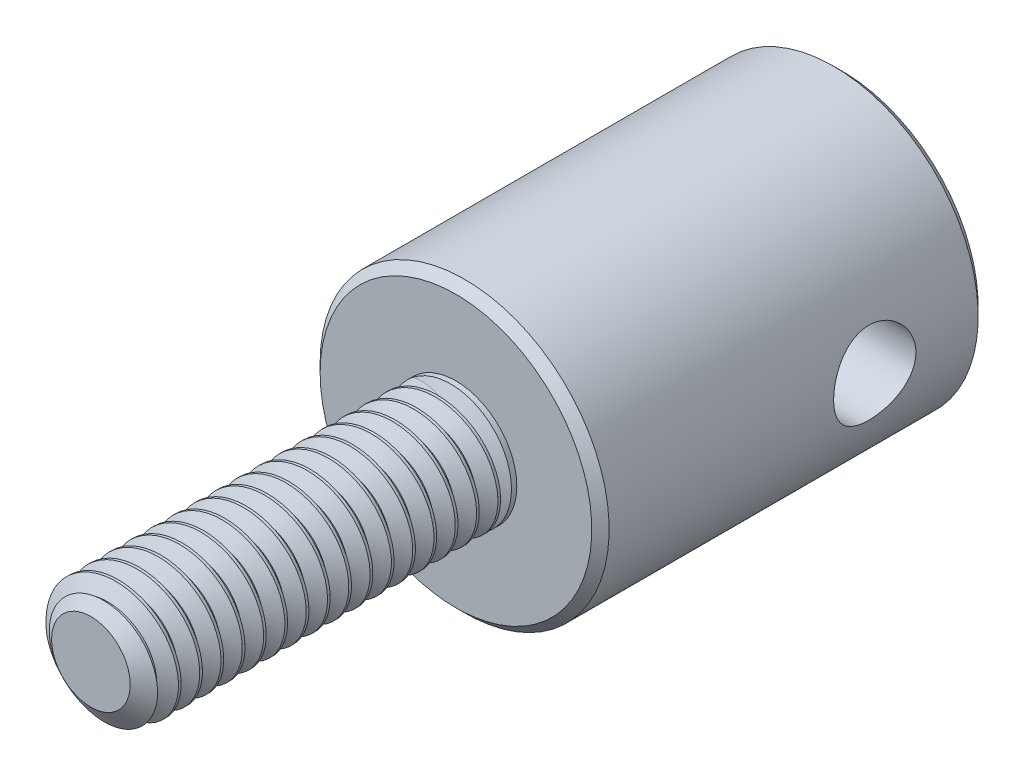
SolidWorks part; units mm, degrees
ref_plane "Front Plane" through (0, 0, 0) normal (0, 0, 1) x (1, 0, 0)
ref_plane "Top Plane" through (0, 0, 0) normal (0, 1, 0) x (1, 0, 0)
ref_plane "Right Plane" through (0, 0, 0) normal (1, 0, 0) x (0, 0, -1)
sketch "Sketch1" plane through (0, 0, 0) normal (0, 0, 1) x (1, 0, 0)
  circle A0 centre (0, 0) radius 2
  dimension "OD" = 4
extrude "Extrude1" add sketch "Sketch1" against normal blind 12
sketch "Sketch2" plane through (0, 0, 0) normal (0, 0, 1) x (1, 0, 0)
  circle A0 centre (0, 0) radius 2 construction
  circle A1 centre (0, 0) radius 2
curve "Helix/Spiral1" pitch 0.7 height 12.7 radius 2 centre (0, 0, 0) axis (0, 0, -1) start towards (0, 1, 0) parameters "pitch"=0.7
sketch "Sketch3" plane through (0, 0, 0) normal (1, 0, 0) x (0, 0, -1)
  line L0 (-0.6125, 2) -> (-0.35, 1.5453)
  line L1 (-0.35, 1.5453) -> (-0.2625, 1.5453)
  line L2 (-0.2625, 1.5453) -> (0, 2)
  line L3 (-0.6125, 2) -> (0, 2)
  line L4 (-0.3063, 2) -> (-0.3063, 1.5453) construction
  line L5 (-0.4813, 1.7727) -> (-0.1313, 1.7727) construction
  line L6 (0, 2) -> (0, -2) construction
  line L7 (0, -2) -> (12, -2) construction
  point P11 (3.15, -2)
  dimension "D1" = 0.0875
  dimension "D2" = 0.35
  dimension "D3" = 60
  dimension "D4" = 3.15
sweep "Cut-Sweep1" cut profiles "Sketch3" path "Helix/Spiral1"
sketch "Sketch4" plane through (0, 0, 0) normal (1, 0, 0) x (0, 0, -1)
  line L0 (0.4962, 2) -> (0, 1.2913)
  line L1 (0, 1.2913) -> (0, 2)
  line L2 (0.4962, 2) -> (0, 2)
  line L3 (-0.6125, 2) -> (0, 2) construction
  line L4 (0, 0) -> (7.0209, 0) construction
  dimension "D1" = 55
  dimension "D2" = 0.254
revolve "Cut-Revolve1" cut sketch "Sketch4" angle 360 about L4
sketch "Sketch5" plane through (0, 0, 0) normal (1, 0, 0) x (0, 0, -1)
  line L0 (12, -0.9741) -> (12, 1.9864) construction
  line L1 (12, 2) -> (0.1203, 2)
  line L2 (12, 2) -> (12, 0)
  line L3 (12, 0) -> (0.0001, 0)
  line L4 (0.0001, 1.6698) -> (0.0001, 0)
  line L5 (0.1203, 2) -> (0.0001, 1.6698)
  line L6 (0, 0) -> (9.9695, 0) construction
  point P3 (0.0001, 2)
  point P10 (0.0001, 2)
  dimension "D1" = 0.3302
  dimension "Thread min" = 0.0001
  dimension "D3" = 20
revolve "partially thread" [suppressed] add sketch "Sketch5" angle 360 about L6
sketch "Sketch6" plane through (0, 0, -12) normal (0, 0, -1) x (-1, 0, 0)
  circle A0 centre (0, 0) radius 4.75
  dimension "head dia" = 9.5
extrude "Extrude2" add sketch "Sketch6" along normal blind 12.7
chamfer "Chamfer1" distance 0.285 angle 45 2 edges at (-4.75, 0, -24.7) (-4.75, 0, -12)
sketch "Sketch9" plane through (0, 0, 0) normal (1, 0, 0) x (0, 0, -1)
  line L0 (0, 2) -> (0, -2) construction
  line L1 (3.85, 2) -> (3.85, -2) construction
  dimension "D1" = 3.85
sketch "Sketch10" plane through (0, 0, 0) normal (1, 0, 0) x (0, 0, -1)
  line L0 (12, 2) -> (12, 0)
  line L1 (12, 2) -> (11.825, 2)
  line L2 (11.825, 2) -> (10.9966, 0)
  line L3 (12, 0) -> (10.9966, 0)
  line L4 (12, 4.465) -> (12, -4.465) construction
  dimension "D1" = 22.5
  dimension "D2" = 0.175
revolve "Revolve1" add sketch "Sketch10" angle 360 about L3
sketch "Sketch11" plane through (0, 0, -24.7) normal (0, 0, -1) x (-1, 0, 0)
  circle A0 centre (0, 0) radius 1.5875
  dimension "D1" = 3.175
extrude "Cut-Extrude1" cut sketch "Sketch11" against normal blind 9.525
chamfer "Chamfer2" distance 0.254 angle 45 1 edges at (-1.5875, 0, -24.7)
ref_plane "Plane1" through (5.08, 0, 0) normal (1, 0, 0) x (0, 0, -1)
sketch "Sketch14" plane through (5.08, 0, 0) normal (1, 0, 0) x (0, 0, -1)
  line L0 (24.7, -4.465) -> (24.7, 4.465) construction
  circle A0 centre (21.017, 0) radius 1.6764
  dimension "D1" = 3.3528
  dimension "D2" = 3.683
hole_wizard "Tap Drill for #6-32 Tap1" positions "Sketch16" profile "Sketch15" hole size "#6-32" standard "ANSI Inch"
sketch "Sketch16" plane through (5.08, 0, 0) normal (1, 0, 0) x (0, 0, -1)
  point P0 (21.017, 0)
sketch "Sketch15" plane through (5.08, 0, -21.017) normal (0, 1, 0) x (0, 0, -1)
  line L0 (0, 0) -> (0, 5.6387)
  line L1 (0, 5.6387) -> (1.3525, 4.826)
  line L2 (1.3525, 4.826) -> (1.3525, 0)
  line L5 (1.3525, 0) -> (0, 0)
  line L10 (0, 5.6387) -> (-1.3526, 4.826) construction
  line L11 (0, -6.35) -> (0, 107.95) construction
  dimension "Hole Dia." = 2.7051
  dimension "Hole Depth" = 4.826
  dimension "Drill Angle" = 118
equation "\"D3@Helix/Spiral1\" = \"screw length@Extrude1\"+\"pitch@Helix/Spiral1\""
equation "\"D1@Sketch3\" = \"pitch@Helix/Spiral1\"*.125"
equation "\"D2@Sketch3\" = \"pitch@Helix/Spiral1\"*.5"
equation "\"D1@Chamfer1\" = \"head dia@Sketch6\" * .03"
equation "\"D1@Sketch9\" = \"pitch@Helix/Spiral1\"*5.5"
equation "\"D2@Sketch10\" = \"pitch@Helix/Spiral1\"*.25"
equation "\"D4@Sketch3\" = \"pitch@Helix/Spiral1\"*4.50"
